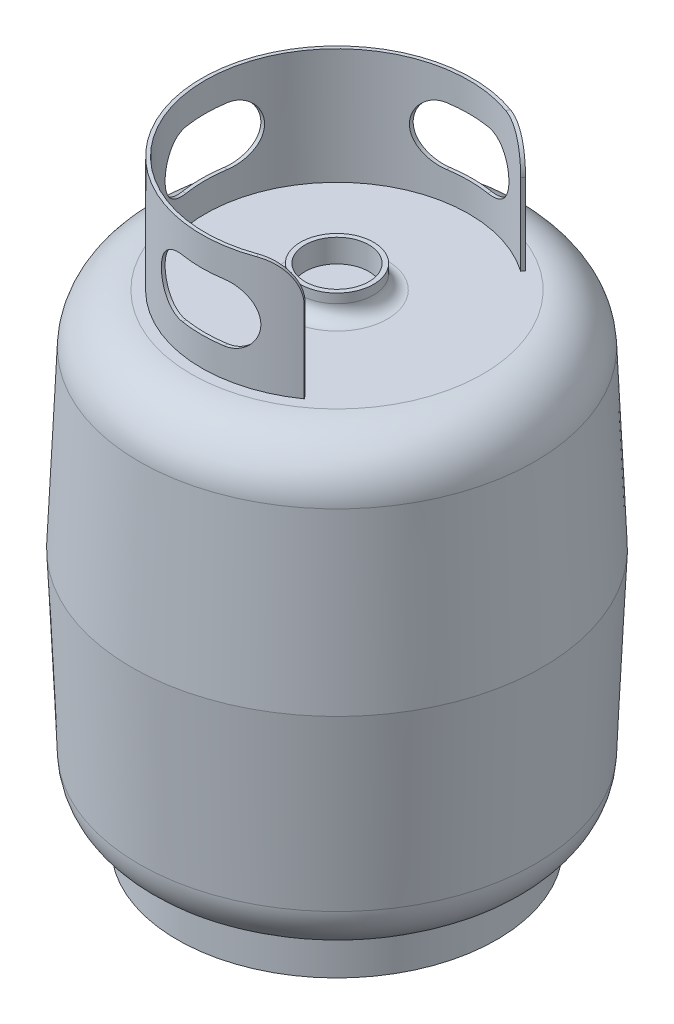
SolidWorks part; units mm, degrees
material "1060 Alloy"
ref_plane "Front Plane" through (0, 0, 0) normal (0, 0, 1) x (1, 0, 0)
ref_plane "Top Plane" through (0, 0, 0) normal (0, 1, 0) x (1, 0, 0)
ref_plane "Right Plane" through (0, 0, 0) normal (1, 0, 0) x (0, 0, -1)
sketch "Sketch1" plane through (0, 0, 0) normal (0, 0, 1) x (1, 0, 0)
  line L0 (-177.5502, 0) -> (164.3684, 0) construction
  line L1 (157.7881, -150.7129) -> (164.3684, 0)
  line L2 (-126.0128, 193.75) -> (-43.5909, 193.75)
  line L3 (-31.5909, 205.75) -> (-31.5909, 213.75)
  line L4 (-31.5909, 213.75) -> (18.4091, 213.75)
  line L5 (18.4091, 213.75) -> (18.4091, 205.75)
  line L6 (30.4091, 193.75) -> (112.831, 193.75)
  line L7 (157.7881, 150.7129) -> (164.3684, 0)
  line L9 (-177.5502, 0) -> (-170.97, 150.7129)
  line L10 (-170.97, 150.7129) -> (157.7881, 150.7129)
  line L11 (30.4091, -193.75) -> (112.831, -193.75)
  line L12 (0, 0) -> (0, -338.2917) construction
  line L13 (-126.0128, -193.75) -> (-43.5909, -193.75)
  line L14 (-177.5502, 0) -> (-170.97, -150.7129)
  line L15 (-43.5909, -193.75) -> (30.4091, -193.75)
  line L16 (0, 251.5348) -> (0, -300.5599)
  arc A0 (112.831, 193.75) -> (157.7881, 150.7129) centre (112.831, 148.75) cw
  arc A1 (-126.0128, 193.75) -> (-170.97, 150.7129) centre (-126.0128, 148.75) ccw
  arc A2 (18.4091, 205.75) -> (30.4091, 193.75) centre (30.4091, 205.75) ccw
  arc A3 (-43.5909, 193.75) -> (-31.5909, 205.75) centre (-43.5909, 205.75) ccw
  arc A4 (112.831, -193.75) -> (157.7881, -150.7129) centre (112.831, -148.75) ccw
  arc A5 (-126.0128, -193.75) -> (-170.97, -150.7129) centre (-126.0128, -148.75) cw
  point P18 (155.9091, 193.75)
  point P21 (-169.0909, 193.75)
  point P24 (18.4091, 193.75)
  point P27 (-31.5909, 193.75)
  dimension "D6" = 164.3684
  dimension "D1" = 45
  dimension "D2" = 12
  dimension "D3" = 18.4091
  dimension "D4" = 112.831
  dimension "D5" = 155.9091
  dimension "D7" = 31.5909
  dimension "D8" = 213.75
revolve "Revolve3" add sketch "Sketch1" angle 360 about L16 region at (-86.3986, -19.9789, 0) region at (-75.1723, 174.2976, 0)
sketch "Sketch2" plane through (0, -193.75, 0) normal (0, -1, 0) x (1, 0, 0)
  circle A0 centre (0, 0) radius 129.0128
  circle A1 centre (0, 0) radius 138.0128
  circle A2 centre (0, 0) radius 126.0128 construction
  dimension "D1" = 3
  dimension "D2" = 12
extrude "Boss-Extrude1" add sketch "Sketch2" along normal blind 30 separate body
sketch "Sketch3" plane through (0, 193.75, 0) normal (0, 1, 0) x (1, 0, 0)
  line L0 (0, 147.5051) -> (0, -148.3756) construction
  line L1 (-142.4505, 0) -> (144.3179, 0) construction
  line L2 (67.1158, 95.8513) -> (65.395, 93.3938)
  line L3 (0, 0) -> (0.349, 0) construction
  line L4 (65.629, -93.2295) -> (67.3498, -95.687)
  line L5 (0.349, 0) -> (0.4491, 0) construction
  arc A0 (65.395, 93.3938) -> (65.629, -93.2295) centre (0, 0) ccw
  circle A1 centre (0, 0) radius 126.0128 construction
  arc A2 (67.1158, 95.8513) -> (67.3498, -95.687) centre (0, 0) ccw
  dimension "D1" = 12
  dimension "D2" = 3
  dimension "D3" = 55
  dimension "D4" = 55
extrude "Boss-Extrude2" add sketch "Sketch3" along normal blind 100
sketch "Sketch4" plane through (0, 0, 0) normal (0, 0, 1) x (1, 0, 0)
  line L0 (65.629, 293.75) -> (-114.0128, 293.75) construction
  line L1 (-18, 243.75) -> (18, 243.75) construction
  line L2 (-18, 268.75) -> (18, 268.75)
  line L3 (-18, 218.75) -> (18, 218.75)
  arc A0 (-18, 268.75) -> (-18, 218.75) centre (-18, 243.75) ccw
  arc A1 (18, 218.75) -> (18, 268.75) centre (18, 243.75) ccw
  point P5 (0, 243.75)
  dimension "D2" = 18
  dimension "D1" = 50
  dimension "D4" = 50
extrude "Cut-Extrude1" cut sketch "Sketch4" against normal mid plane 350
sketch "Sketch5" plane through (0, 213.75, 0) normal (0, 1, 0) x (1, 0, 0)
  circle A0 centre (0, 0) radius 27.5909
  circle A1 centre (0, 0) radius 31.5909 construction
  dimension "D1" = 4
extrude "Cut-Extrude2" cut sketch "Sketch5" against normal blind 20
sketch "Sketch6" plane through (0, 0, 0) normal (1, 0, 0) x (0, 0, -1)
  line L0 (0, 0) -> (0, 347.1431) construction
  line L1 (-18, 243.75) -> (18, 243.75) construction
  line L2 (-18, 268.75) -> (18, 268.75)
  line L3 (-18, 218.75) -> (18, 218.75)
  line L4 (114.0128, 293.75) -> (-114.0128, 293.75) construction
  arc A0 (-18, 268.75) -> (-18, 218.75) centre (-18, 243.75) ccw
  arc A1 (18, 218.75) -> (18, 268.75) centre (18, 243.75) ccw
  point P5 (0, 243.75)
  dimension "D1" = 50
  dimension "D2" = 18
  dimension "D3" = 50
extrude "Cut-Extrude4" cut sketch "Sketch6" against normal blind 200
fillet "Fillet1" radius 30 2 edges at (66.2554, 293.75, -94.6225) (66.4894, 293.75, 94.4583)
equation "\"A\"= 325.0'A"
equation "\"B\" = 387.50'B"
